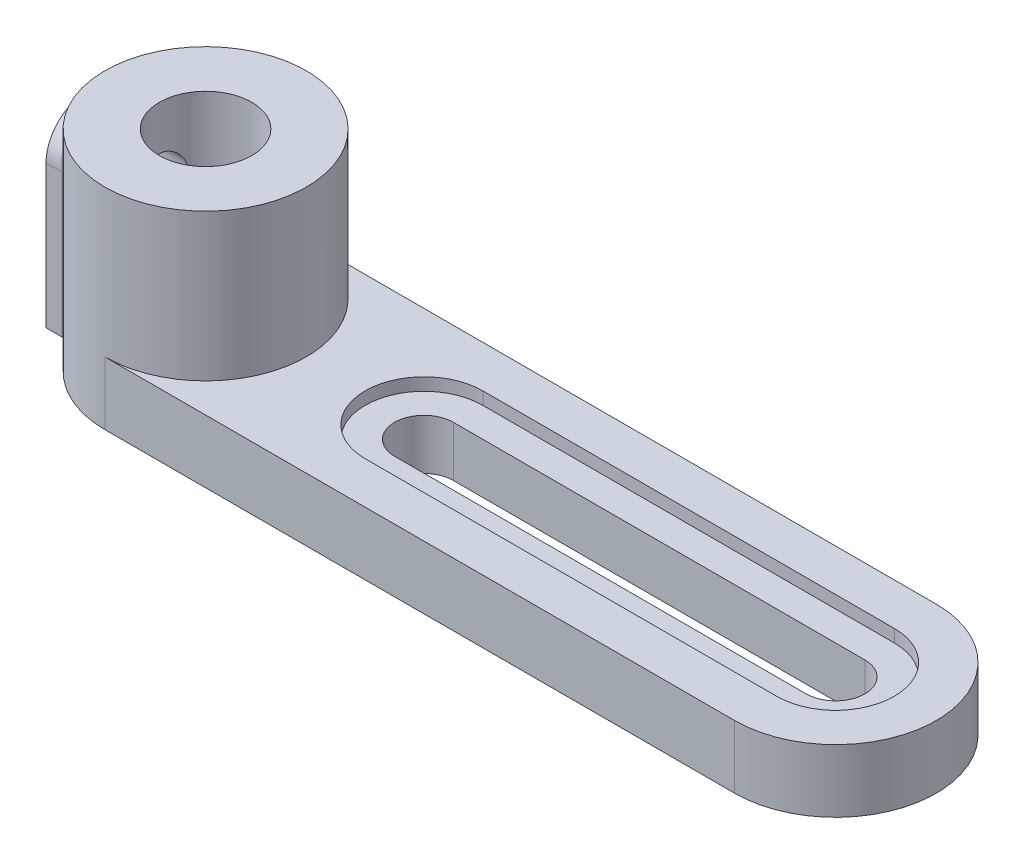
SolidWorks part; units mm, degrees
ref_plane "Front Plane" through (0, 0, 0) normal (0, 0, 1) x (1, 0, 0)
ref_plane "Top Plane" through (0, 0, 0) normal (0, 1, 0) x (1, 0, 0)
ref_plane "Right Plane" through (0, 0, 0) normal (1, 0, 0) x (0, 0, -1)
sketch "Sketch1" plane through (0, 0, 0) normal (0, 1, 0) x (1, 0, 0)
  line L0 (-75, 0) -> (75, 0) construction
  line L1 (-75, 24) -> (75, 24)
  line L2 (-75, -24) -> (75, -24)
  arc A0 (-75, 24) -> (-75, -24) centre (-75, 0) ccw
  arc A1 (75, -24) -> (75, 24) centre (75, 0) ccw
  point P2 (0, 0)
  dimension "D1" = 24
  dimension "D2" = 150
extrude "Boss-Extrude1" add sketch "Sketch1" along normal blind 15
sketch "Sketch2" plane through (0, 15, 0) normal (0, 1, 0) x (1, 0, 0)
  circle A0 centre (-75, 0) radius 24
  arc A1 (-75, 24) -> (-75, -24) centre (-75, 0) ccw construction
extrude "Boss-Extrude2" add sketch "Sketch2" along normal blind 35
sketch "Sketch3" plane through (0, 15, 0) normal (0, 1, 0) x (1, 0, 0)
  line L0 (75, 0) -> (-23, 0) construction
  line L3 (75, -7) -> (-23, -7)
  line L4 (75, 7) -> (-23, 7)
  arc A2 (75, -7) -> (75, 7) centre (75, 0) ccw
  arc A3 (-23, 7) -> (-23, -7) centre (-23, 0) ccw
  point P3 (26, 0)
  dimension "D1" = 7
  dimension "D2" = 98
extrude "Cut-Extrude1" cut sketch "Sketch3" against normal blind 35
sketch "Sketch4" plane through (0, 15, 0) normal (0, 1, 0) x (1, 0, 0)
  line L0 (75, 0) -> (-23, 0) construction
  line L1 (75, -14) -> (-23, -14)
  line L2 (75, 14) -> (-23, 14)
  arc A0 (75, -14) -> (75, 14) centre (75, 0) ccw
  arc A1 (-23, 14) -> (-23, -14) centre (-23, 0) ccw
  point P4 (26, 0)
  dimension "D1" = 14
extrude "Cut-Extrude2" cut sketch "Sketch4" against normal blind 3
ref_plane "Plane1" through (-103, 0, 0) normal (1, 0, 0) x (0, 0, -1)
sketch "Sketch5" plane through (-103, 0, 0) normal (1, 0, 0) x (0, 0, -1)
  line L0 (-24, 0) -> (24, 0) construction
  line L1 (-10, 0) -> (10, 0)
  line L2 (10, 34) -> (10, 0)
  line L3 (-10, 34) -> (-10, 0)
  arc A0 (10, 34) -> (-10, 34) centre (0, 34) ccw
  dimension "D1" = 20
  dimension "D2" = 34
extrude "Boss-Extrude3" add sketch "Sketch5" along normal up to next
hole_wizard "Hole1" positions "Sketch6" profile "Sketch7" legacy end condition through all
sketch "Sketch6" plane through (0, 50, 0) normal (0, 1, 0) x (1, 0, 0)
  point P0 (-75, 0)
sketch "Sketch7" plane through (-75, 50, 0) normal (1, 0, 0) x (0, 0, 1)
  line L0 (0, 0) -> (0, 50)
  line L1 (0, 50) -> (11, 50)
  line L2 (11, 50) -> (11, 0)
  line L3 (11, 0) -> (0, 0)
  line L4 (0, 110) -> (0, -10) construction
  dimension "Diameter" = 22
  dimension "Depth" = 50
hole_wizard "M12x1.25 Tapped Hole1" positions "Sketch8" profile "Sketch9" tap size "M12x1.25" standard "ANSI Metric" end condition up to next
sketch "Sketch8" plane through (-103, 0, 0) normal (-1, 0, 0) x (0, 0, 1)
  point P0 (0, 34)
  point P4 (0, 0)
sketch "Sketch9" plane through (-103, 34, 0) normal (0, 1, 0) x (0, 0, 1)
  line L0 (0, 0) -> (0, 17)
  line L1 (0, 17) -> (5.4, 17)
  line L2 (5.4, 17) -> (5.4, 0.625)
  line L3 (5.4, 0.625) -> (6.025, 0)
  line L5 (6.025, 0) -> (0, 0)
  line L6 (-5.4, 0.625) -> (-6.025, 0) construction
  line L11 (0, -6.35) -> (0, 107.95) construction
  dimension "Thru Tap Drill Dia." = 10.8
  dimension "Thru Tap Drill Depth" = 17
  dimension "Near C'Sink Dia." = 12.05
  dimension "Near C'Sink Angle" = 90
cosmetic thread "Hole Thread1" parameters "D2"=12
fillet "Fillet1" radius 4 3 edges at (-96.8174, 17, -10) (-98.988, 43.9713, 0.7573) (-96.8174, 17, 10)
